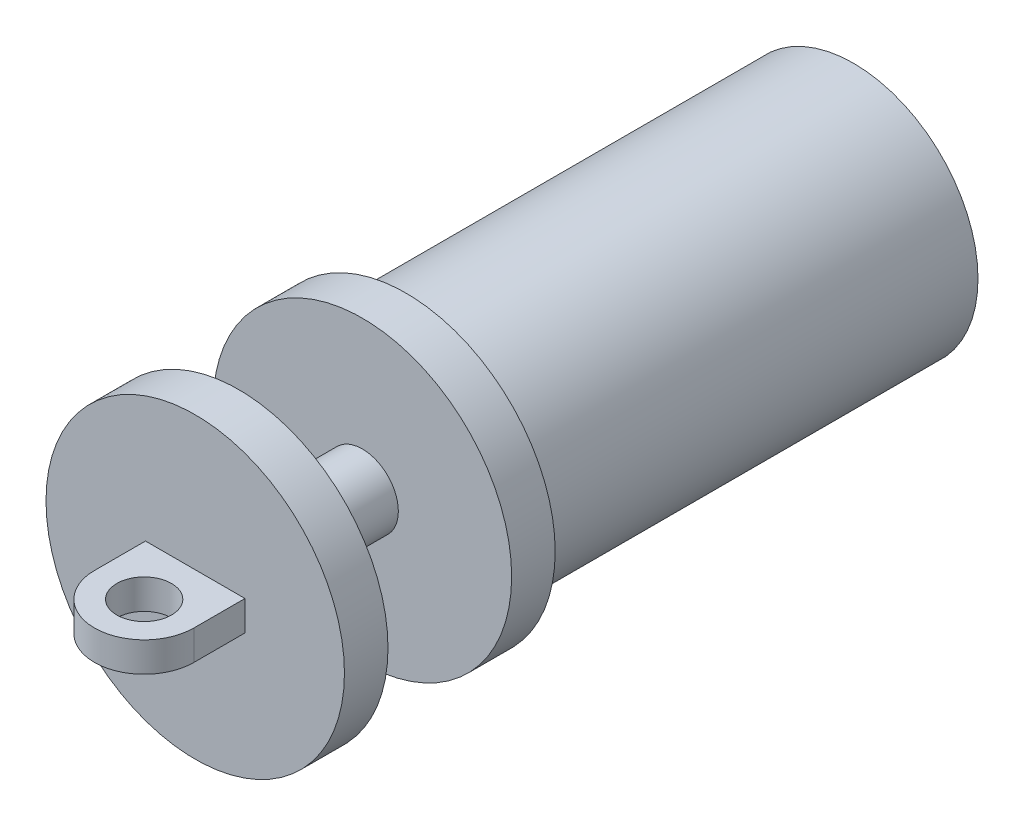
SolidWorks part; units mm, degrees
ref_plane "Front Plane" through (0, 0, 0) normal (0, 0, 1) x (1, 0, 0)
ref_plane "Top Plane" through (0, 0, 0) normal (0, 1, 0) x (1, 0, 0)
ref_plane "Right Plane" through (0, 0, 0) normal (1, 0, 0) x (0, 0, -1)
sketch "Sketch2" plane through (0, 0, 0) normal (0, 0, 1) x (1, 0, 0)
  circle A0 centre (0, 0) radius 15
  dimension "D1" = 30
sketch "Sketch3" plane through (0, 0, 0) normal (1, 0, 0) x (0, 0, -1)
  line L0 (-6.2146, 3.6112) -> (6.2146, 3.6112)
  line L1 (10.591, 15) -> (6.2146, 15)
  line L2 (10.591, 15) -> (10.591, 0)
  line L4 (-10.591, 15) -> (-10.591, 0)
  line L5 (10.591, 15) -> (0, 0) construction
  line L6 (0, 0) -> (-10.591, 15) construction
  line L7 (-6.2146, 15) -> (-6.2146, 3.6112)
  line L8 (0, 15) -> (0, -15) construction
  line L9 (55, 0) -> (-55, 0) construction
  line L10 (-10.591, 0) -> (10.591, 0) construction
  line L13 (0, 55) -> (0, -55) construction
  line L15 (6.2146, 15) -> (6.2146, 3.6112)
  line L16 (-6.2146, 15) -> (-10.591, 15)
  line L18 (-10.591, 0) -> (10.591, 0)
  point P18 (0, -3.6112)
  point P19 (0, 3.6112)
revolve "Revolve2" add sketch "Sketch3" angle 360 about L18
sketch "Sketch4" plane through (0, 0, 0) normal (0, 1, 0) x (1, 0, 0)
  line L0 (-5, -15.7238) -> (-5, -10.591)
  line L1 (-15, -10.591) -> (15, -10.591) construction
  line L2 (-5, -10.591) -> (5, -10.591)
  line L3 (5, -10.591) -> (5, -15.7238)
  circle A0 centre (0, -15.7238) radius 2.75
  arc A1 (-5, -15.7238) -> (5, -15.7238) centre (0, -15.7238) ccw
  dimension "D1" = 5.5
  dimension "D2" = 10
extrude "Boss-Extrude1" add sketch "Sketch4" along normal mid plane 3
sketch "Sketch5" plane through (0, 0, -10.591) normal (0, 0, -1) x (-1, 0, 0)
  circle A0 centre (0, 0) radius 12.5
  dimension "D1" = 25
extrude "Boss-Extrude2" add sketch "Sketch5" along normal blind 45
